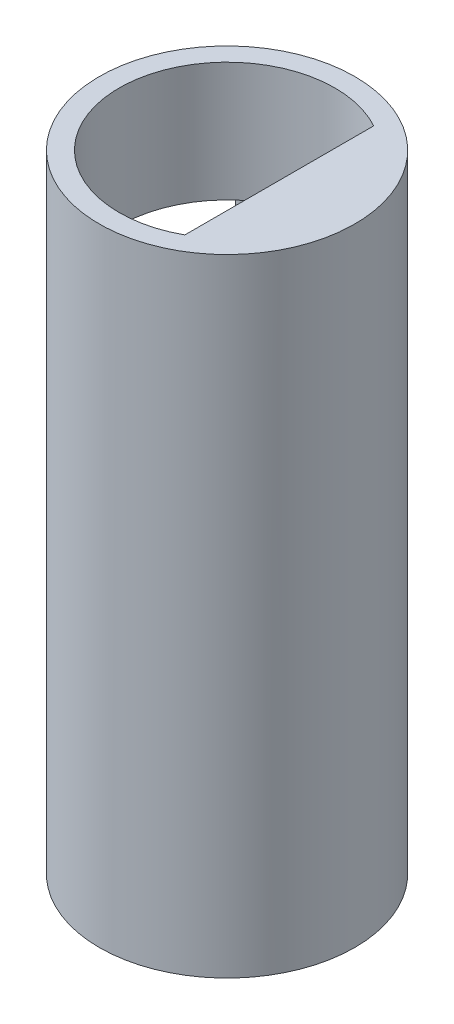
SolidWorks part; units mm, degrees
ref_plane "Front Plane" through (0, 0, 0) normal (0, 0, 1) x (1, 0, 0)
ref_plane "Top Plane" through (0, 0, 0) normal (0, 1, 0) x (1, 0, 0)
ref_plane "Right Plane" through (0, 0, 0) normal (1, 0, 0) x (0, 0, -1)
sketch "Sketch1" plane through (0, 0, 0) normal (0, 1, 0) x (1, 0, 0)
  circle A1 centre (0, 0) radius 46.609
  dimension "D1" = 93.218
extrude "Boss-Extrude1" add sketch "Sketch1" along normal blind 25.4
sketch "Sketch4" plane through (0, 25.4, 0) normal (0, 1, 0) x (1, 0, 0)
  line L0 (19.05, 42.5382) -> (19.05, -42.5382)
  circle A0 centre (0, 0) radius 46.609 construction
  arc A1 (19.05, 42.5382) -> (19.05, -42.5382) centre (0, 0) cw
  dimension "D1" = 19.05
extrude "Boss-Extrude2" add sketch "Sketch4" along normal blind 203.2
sketch "Sketch5" plane through (19.05, 0, 0) normal (-1, 0, 0) x (0, 0, 1)
  line L0 (-42.5382, 228.6) -> (42.5382, 228.6) construction
  line L1 (-26.67, 172.085) -> (26.67, 172.085)
  line L2 (-26.67, 172.085) -> (-26.67, 81.915)
  line L3 (-26.67, 81.915) -> (26.67, 81.915)
  line L4 (26.67, 172.085) -> (26.67, 81.915)
  line L5 (42.5382, 228.6) -> (42.5382, 25.4) construction
  circle A0 centre (-26.67, 172.085) radius 1.1049
  circle A1 centre (26.67, 172.085) radius 1.1049
  circle A2 centre (26.67, 81.915) radius 1.1049
  circle A3 centre (-26.67, 81.915) radius 1.1049
  point P4 (0, 172.085)
  point P7 (0, 228.6)
  point P8 (26.67, 127)
  point P11 (42.5382, 127)
  dimension "D5" = 2.2098
  dimension "D6" = 2.2098
  dimension "D7" = 2.2098
  dimension "D8" = 2.2098
  dimension "D1" = 0
  dimension "D2" = 0
  dimension "D3" = 90.17
  dimension "D4" = 53.34
extrude "Cut-Extrude1" cut sketch "Sketch5" against normal blind 15.24 contours L1 A0 L2 | L2 A0 L1 | L1 A1 L4 | L4 A1 L1 | A2 | A3 region at (19.05, 172.2413, -26.8263) region at (19.05, 171.6161, -26.2011) region at (19.05, 172.2413, 26.8263) region at (19.05, 171.6161, 26.2011)
sketch "Sketch9" plane through (0, 228.6, 0) normal (0, 1, 0) x (1, 0, 0)
  circle A0 centre (0, 0) radius 46.609
  circle A1 centre (0, 0) radius 39.37
  dimension "D1" = 93.218
  dimension "D2" = 78.74
extrude "Boss-Extrude5" add sketch "Sketch9" against normal up to surface (203.2 mm away) up to face at (-13.7795, 25.4, 0)
sketch "Sketch11" plane through (19.05, 0, 0) normal (-1, 0, 0) x (0, 0, 1)
  line L0 (-34.4542, 25.4) -> (-34.4542, 228.6) construction
  line L1 (-34.4542, 185.0579) -> (34.4542, 185.0579)
  line L2 (-34.4542, 185.0579) -> (-34.4542, 50.4379)
  line L3 (-34.4542, 50.4379) -> (34.4542, 50.4379)
  line L4 (34.4542, 185.0579) -> (34.4542, 50.4379)
  line L5 (34.4542, 228.6) -> (34.4542, 25.4) construction
  line L6 (-34.4542, 25.4) -> (34.4542, 25.4) construction
  line L7 (-34.4542, 162.56) -> (34.4542, 162.56)
  line L8 (-34.4542, 162.56) -> (-34.4542, 137.16)
  line L9 (-34.4542, 137.16) -> (34.4542, 137.16)
  line L10 (34.4542, 162.56) -> (34.4542, 137.16)
  circle M9 centre (-26.67, 81.915) radius 1.1049
  circle M10 centre (26.67, 81.915) radius 1.1049
  circle M11 centre (26.67, 172.085) radius 1.1049
  circle M12 centre (-26.67, 172.085) radius 1.1049
  line M13 (-34.4542, 228.6) -> (-34.4542, 25.4)
  line M15 (34.4542, 25.4) -> (34.4542, 228.6)
  dimension "D1" = 25.4
  dimension "D2" = 137.16
  dimension "D3" = 134.62
extrude "Cut-Extrude3" cut sketch "Sketch11" along normal blind 154.686 contours L7 L4 L1 M13 M11 M12 | M12 | L9 L3 M13 M15 M10 M9 | M11 | M10 | M9 region at (19.05, 173.8175, 0) region at (19.05, 93.8142, 0) region at (19.05, 81.915, -26.67) region at (19.05, 81.915, 26.67) region at (19.05, 172.085, 26.67) region at (19.05, 172.085, -26.67)
